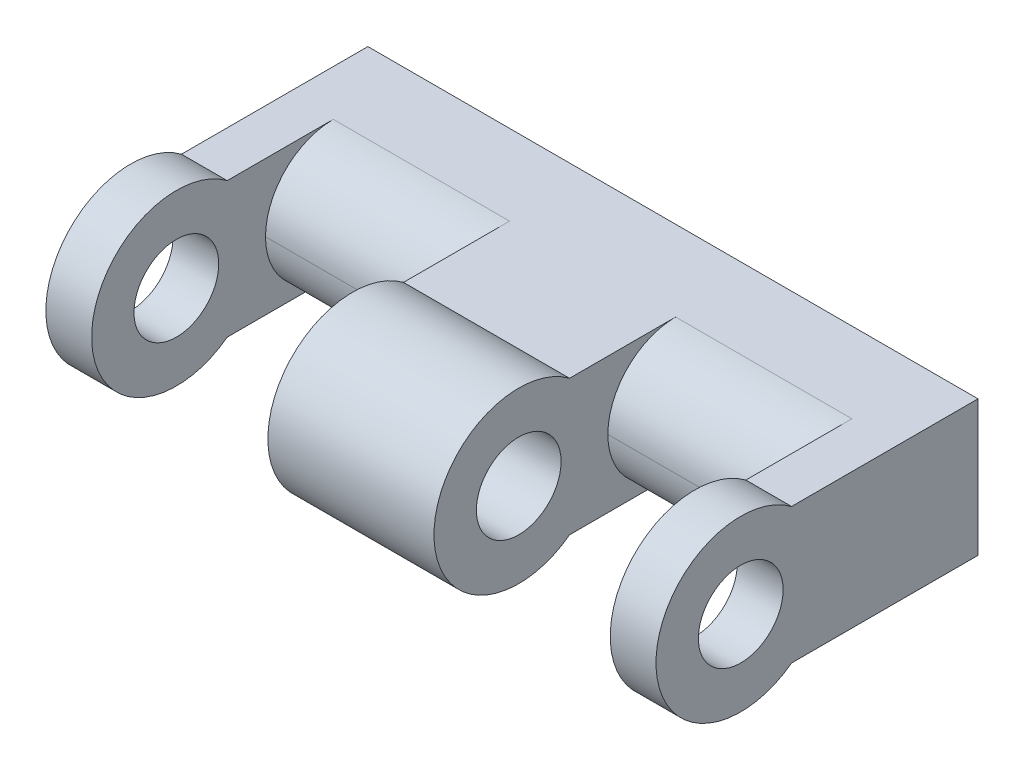
SolidWorks part; units mm, degrees
ref_plane "Front Plane" through (0, 0, 0) normal (0, 0, 1) x (1, 0, 0)
ref_plane "Top Plane" through (0, 0, 0) normal (0, 1, 0) x (1, 0, 0)
ref_plane "Right Plane" through (0, 0, 0) normal (1, 0, 0) x (0, 0, -1)
sketch "Sketch1" plane through (0, 0, 0) normal (0, 0, 1) x (1, 0, 0)
  line L1 (0, 0) -> (180, 0)
  line L2 (0, 0) -> (0, 40)
  line L3 (0, 40) -> (180, 40)
  line L4 (180, 0) -> (180, 40)
extrude "Boss-Extrude1" add sketch "Sketch1" along normal blind 56
sketch "Sketch2" plane through (0, 0, 0) normal (0, 0, -1) x (-1, 0, 0)
  line L1 (-165, 15) -> (-15, 15)
  line L2 (-165, 15) -> (-165, 25)
  line L3 (-165, 25) -> (-15, 25)
  line L4 (-15, 15) -> (-15, 25)
extrude "Cut-Extrude1" cut sketch "Sketch2" against normal blind 40
ref_plane "Plane1" through (90, 0, 0) normal (1, 0, 0) x (0, 0, -1)
sketch "Sketch3" plane through (90, 0, 0) normal (1, 0, 0) x (0, 0, -1)
  circle A0 centre (-70, 20) radius 25
extrude "Boss-Extrude2" add sketch "Sketch3" along normal blind 24.5 contours A0
sketch "Sketch4" plane through (180, 0, 0) normal (1, 0, 0) x (0, 0, -1)
  circle A0 centre (-70, 20) radius 25
extrude "Boss-Extrude3" add sketch "Sketch4" against normal blind 13.5
sketch "Sketch6" plane through (180, 0, 0) normal (1, 0, 0) x (0, 0, -1)
  circle A0 centre (-70, 20) radius 12.5
extrude "Cut-Extrude2" cut sketch "Sketch6" against normal blind 90
mirror "Mirror1" about plane through (90, 0, 0) normal (1, 0, 0) of "Cut-Extrude2", "Boss-Extrude3", "Boss-Extrude2"
sketch "Sketch10" plane through (114.5, 0, 0) normal (1, 0, 0) x (0, 0, -1)
  line L0 (-55, 0) -> (0, 0) construction
  line L1 (-55, 40) -> (-43.7014, 40)
  line L2 (-55, 40) -> (-55, 0)
  line L3 (-55, 0) -> (-43.7014, 0)
  line L4 (-43.7014, 40) -> (-43.7014, 0)
extrude "Cut-Extrude4" cut sketch "Sketch10" along normal blind 52
mirror "Mirror3" about plane through (90, 0, 0) normal (1, 0, 0) of "Cut-Extrude4"
sketch "Sketch11" plane through (0, 0, 56) normal (0, 0, 1) x (1, 0, 0)
  line L1 (114.5, 40) -> (166.5, 40)
  line L2 (114.5, 40) -> (114.5, 0)
  line L3 (114.5, 0) -> (166.5, 0)
  line L4 (166.5, 40) -> (166.5, 0)
extrude "Cut-Extrude5" cut sketch "Sketch11" against normal blind 2 contours L3 L4 L1 L2
mirror "Mirror4" about plane through (90, 0, 0) normal (1, 0, 0) of "Cut-Extrude5"
fillet "Fillet1" radius 20 4 edges at (39.5, 40, 43.7014) (39.5, 0, 43.7014) (140.5, 40, 43.7014) (140.5, 0, 43.7014)
